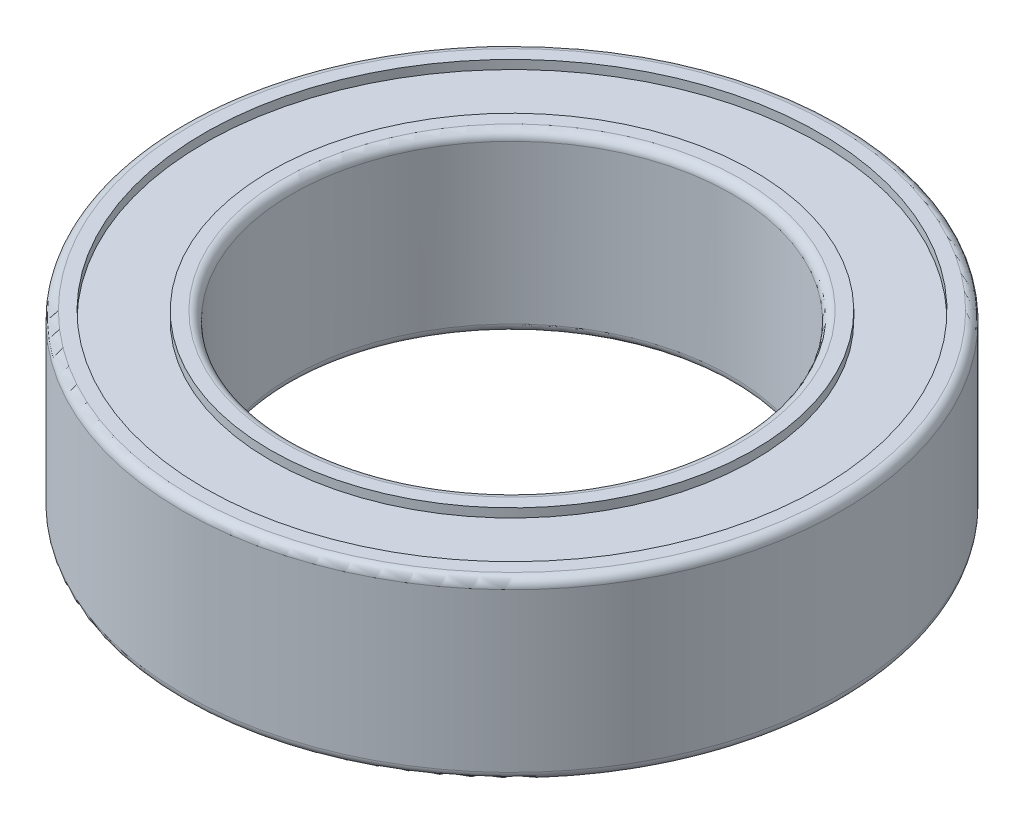
SolidWorks part; units mm, degrees
ref_plane "Front Plane" through (0, 0, 0) normal (0, 0, 1) x (1, 0, 0)
ref_plane "Top Plane" through (0, 0, 0) normal (0, 1, 0) x (1, 0, 0)
ref_plane "Right Plane" through (0, 0, 0) normal (1, 0, 0) x (0, 0, -1)
sketch "Sketch1" plane through (0, 0, 0) normal (1, 0, 0) x (0, 0, -1)
  line L0 (5, 2) -> (5, -2)
  line L1 (5, -2) -> (5.5, -2)
  line L2 (5.5, -2) -> (5.5, -1.8)
  line L3 (5.5, -1.8) -> (7, -1.8)
  line L4 (7, -1.8) -> (7, -2)
  line L5 (7, -2) -> (7.5, -2)
  line L6 (7.5, -2) -> (7.5, 2)
  line L7 (7.5, 2) -> (7, 2)
  line L8 (7, 2) -> (7, 1.8)
  line L9 (7, 1.8) -> (5.5, 1.8)
  line L10 (5.5, 1.8) -> (5.5, 2)
  line L11 (5.5, 2) -> (5, 2)
  line L12 (5, 0) -> (0, 0) construction
  line L13 (0, 1.1937) -> (0, 0) construction
  dimension "D1" = 15
  dimension "D2" = 10
  dimension "D3" = 0.5
  dimension "D4" = 0.2
  dimension "D5" = 4
revolve "Revolve1" add sketch "Sketch1" angle 360 about L13
fillet "Fillet1" radius 0.2 4 edges at (0, 2, 5) (0, -2, 5) (0, -2, 7.5) (0, 2, 7.5)
sketch "Sketch2" plane through (0, -1.8, 0) normal (0, -1, 0) x (1, 0, 0)
  circle A1 centre (0, 0) radius 5.5 construction
  circle A2 centre (0, 0) radius 7
  circle A3 centre (0, 0) radius 7
  circle A4 centre (0, 0) radius 5.5
  dimension "D1" = 0
extrude "Boss-Extrude1" [suppressed] add sketch "Sketch2" along normal up to surface (0.2 mm away)
ref_axis "Axis1" [suppressed] through (0, -2.3225, 0) along (0, 1, 0)
